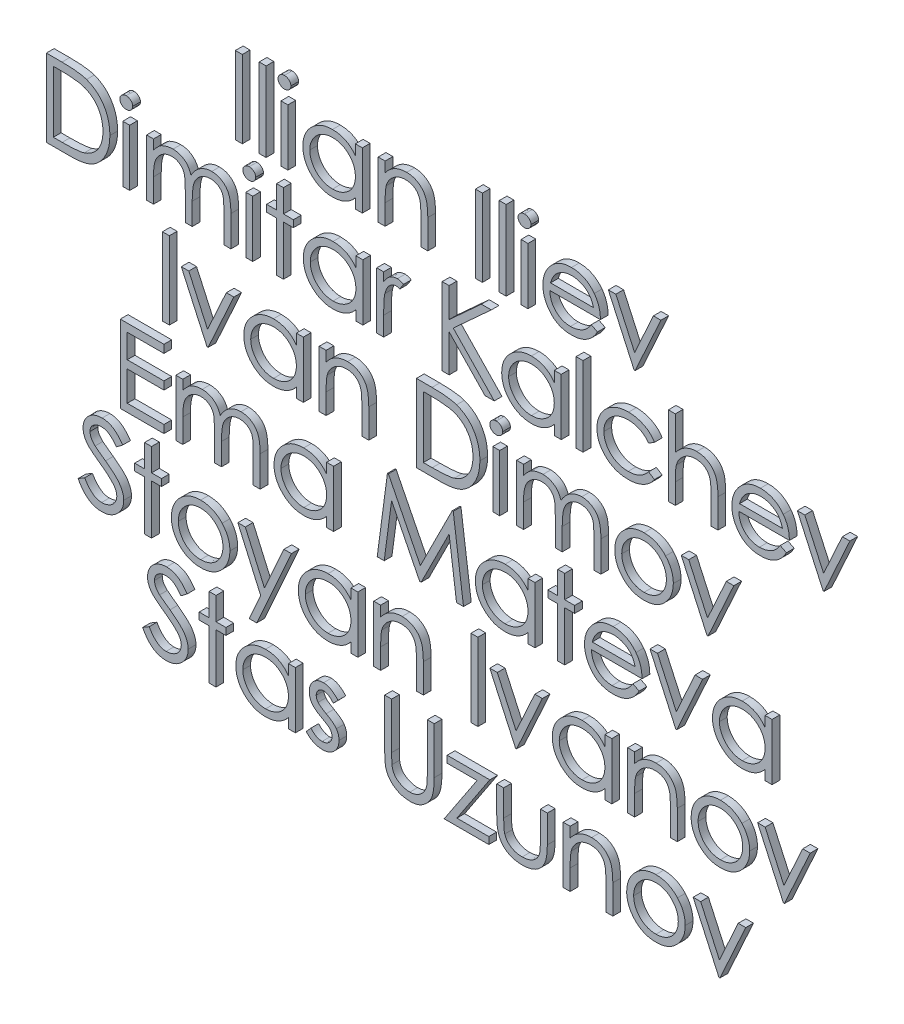
SolidWorks part; units mm, degrees
ref_plane "Front Plane" through (0, 0, 0) normal (0, 0, 1) x (1, 0, 0)
ref_plane "Top Plane" through (0, 0, 0) normal (0, 1, 0) x (1, 0, 0)
ref_plane "Right Plane" through (0, 0, 0) normal (1, 0, 0) x (0, 0, -1)
sketch "Sketch1" plane through (0, 0, 0) normal (0, 0, 1) x (1, 0, 0)
  line L0 (-459.2063, 194.0473) -> (390.7937, 194.0473) construction
  line L1 (-459.2063, 131.5473) -> (390.7937, 131.5473) construction
  line L2 (390.7937, 69.0473) -> (-459.2063, 69.0473) construction
  line L3 (-459.2063, 6.5473) -> (390.7937, 6.5473) construction
  line L4 (390.7937, -55.9527) -> (-459.2063, -55.9527) construction
  line L5 (-459.2063, -118.4527) -> (390.7937, -118.4527) construction
  line L6 (390.7937, -180.9527) -> (-459.2063, -180.9527) construction
  text T0 "Ilian Iliev" font "Century Gothic" height 50
  text T1 "Dimitar Kalchev" font "Century Gothic" height 50
  text T2 "Ivan Dimov" font "Century Gothic" height 50
  text T3 "Ema Mateva" font "Century Gothic" height 50
  text T4 "Stoyan Ivanov" font "Century Gothic" height 50
  text T5 "Stas Uzunov" font "Century Gothic" height 50
  dimension "D1" = 62.5
  dimension "D2" = 62.5
  dimension "D3" = 62.5
  dimension "D4" = 62.5
  dimension "D5" = 62.5
  dimension "D6" = 62.5
extrude "Boss-Extrude1" add sketch "Sketch1" along normal blind 5
